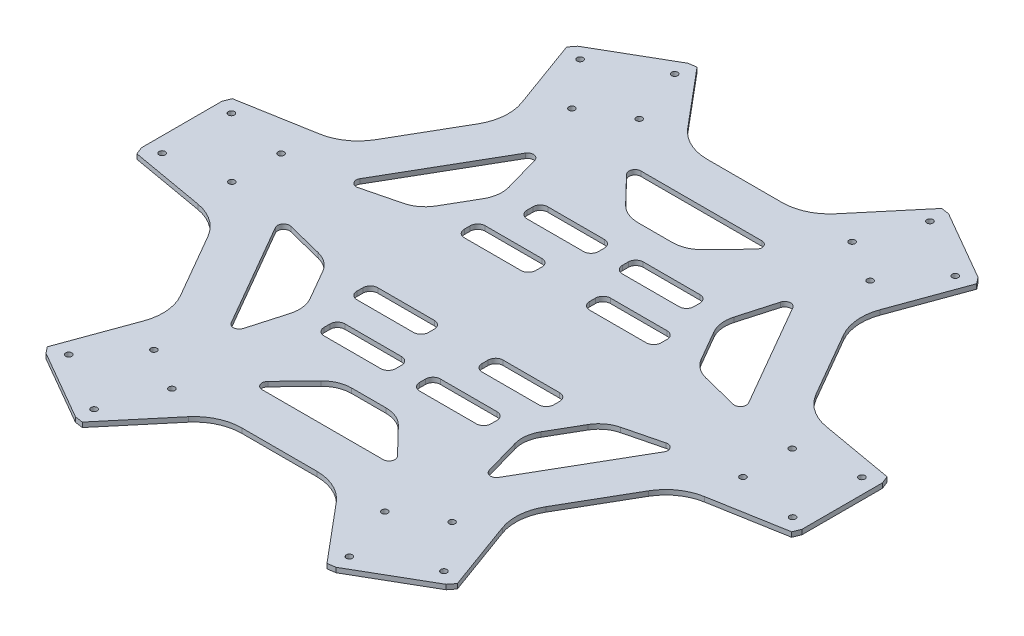
SolidWorks part; units mm, degrees
ref_plane "Front Plane" through (0, 0, 0) normal (0, 0, 1) x (1, 0, 0)
ref_plane "Top Plane" through (0, 0, 0) normal (0, 1, 0) x (1, 0, 0)
ref_plane "Right Plane" through (0, 0, 0) normal (1, 0, 0) x (0, 0, -1)
sketch "Sketch2" plane through (0, 0, 0) normal (0, 1, 0) x (1, 0, 0)
  line L0 (-110.75, -13.5) -> (-110.75, 13.5)
  line L1 (110.75, 0) -> (55.375, 95.9123) construction
  line L2 (55.375, 95.9123) -> (-55.375, 95.9123) construction
  line L3 (-55.375, 95.9123) -> (-110.75, 0) construction
  line L4 (-110.75, 0) -> (-55.375, -95.9123) construction
  line L5 (-55.375, -95.9123) -> (55.375, -95.9123) construction
  line L6 (55.375, -95.9123) -> (110.75, 0) construction
  line L7 (-110.75, 0) -> (0, 0) construction
  line L14 (0, 0) -> (0, 78) construction
  line L15 (-67.55, 39) -> (-90.0666, 0) construction
  line L16 (0, 78) -> (-67.55, 39) construction
  line L17 (-67.55, 39) -> (-67.55, -39) construction
  line L18 (-67.55, -39) -> (0, -78) construction
  line L19 (0, -78) -> (67.55, -39) construction
  line L20 (67.55, -39) -> (67.55, 39) construction
  line L21 (67.55, 39) -> (0, 78) construction
  line L22 (-110.75, 13.5) -> (-109.75, 13.5) construction
  line L23 (-67.55, 39) -> (-77.5583, 21.6651)
  line L24 (-109.75, 13.5) -> (-109.75, 16) construction
  line L25 (-110.75, 13.5) -> (-109.75, 16)
  line L26 (-77.5583, 21.6651) -> (-78.8083, 19.5) construction
  line L27 (-109.75, 16) -> (-77.5583, 21.6651)
  line L28 (-110.75, -13.5) -> (-109.75, -16)
  line L29 (-109.75, -16) -> (-77.5583, -21.6651)
  line L30 (-67.55, -39) -> (-77.5583, -21.6651)
  line L31 (-67.55, 39) -> (-57.5417, 56.3349)
  line L32 (-68.7314, 87.0463) -> (-57.5417, 56.3349)
  line L33 (-67.0663, 89.1623) -> (-68.7314, 87.0463)
  line L34 (-67.0663, 89.1623) -> (-43.6837, 102.6623)
  line L35 (-43.6837, 102.6623) -> (-41.0186, 103.0463)
  line L36 (-41.0186, 103.0463) -> (-20.0167, 78)
  line L37 (0, 78) -> (-20.0167, 78)
  line L38 (0, 78) -> (20.0167, 78)
  line L39 (41.0186, 103.0463) -> (20.0167, 78)
  line L40 (43.6837, 102.6623) -> (41.0186, 103.0463)
  line L41 (43.6837, 102.6623) -> (67.0663, 89.1623)
  line L42 (67.0663, 89.1623) -> (68.7314, 87.0463)
  line L43 (68.7314, 87.0463) -> (57.5417, 56.3349)
  line L44 (67.55, 39) -> (57.5417, 56.3349)
  line L45 (67.55, 39) -> (77.5583, 21.6651)
  line L46 (109.75, 16) -> (77.5583, 21.6651)
  line L47 (110.75, 13.5) -> (109.75, 16)
  line L48 (110.75, 13.5) -> (110.75, -13.5)
  line L49 (110.75, -13.5) -> (109.75, -16)
  line L50 (109.75, -16) -> (77.5583, -21.6651)
  line L51 (67.55, -39) -> (77.5583, -21.6651)
  line L52 (67.55, -39) -> (57.5417, -56.3349)
  line L53 (68.7314, -87.0463) -> (57.5417, -56.3349)
  line L54 (67.0663, -89.1623) -> (68.7314, -87.0463)
  line L55 (67.0663, -89.1623) -> (43.6837, -102.6623)
  line L56 (43.6837, -102.6623) -> (41.0186, -103.0463)
  line L57 (41.0186, -103.0463) -> (20.0167, -78)
  line L58 (0, -78) -> (20.0167, -78)
  line L59 (0, -78) -> (-20.0167, -78)
  line L60 (-41.0186, -103.0463) -> (-20.0167, -78)
  line L61 (-43.6837, -102.6623) -> (-41.0186, -103.0463)
  line L62 (-43.6837, -102.6623) -> (-67.0663, -89.1623)
  line L63 (-67.0663, -89.1623) -> (-68.7314, -87.0463)
  line L64 (-68.7314, -87.0463) -> (-57.5417, -56.3349)
  line L65 (-67.55, -39) -> (-57.5417, -56.3349)
  circle A0 centre (0, 0) radius 95.9123 construction
  circle A1 centre (0, 0) radius 67.55 construction
  point P67 (0, 0)
  dimension "D1" = 110.75
  dimension "D2" = 13.5
  dimension "D3" = 78
  dimension "D4" = 1
  dimension "D5" = 2.5
  dimension "D6" = 2.5
  dimension "D7" = 6
extrude "Base plate" add sketch "Sketch2" along normal blind 1.6 contours L30 L65 L64 L63 L62 L61 L60 L59 L58 L57 L56 L55 L54 L53 L52 L51 L50 L49 L48 L47 L46 L45 L44 L43 L42 L41 L40 L39 L38 L37 L36 L35 L34 L33 L32 L31 L23 L27 L25 L0 L28 L29 region at (0, 0, 0)
fillet "Fillet3" radius 16 12 edges at (-57.5417, 0.8, 56.3349) (-77.5583, 0.8, 21.6651) (-20.0167, 0.8, 78) (20.0167, 0.8, 78) (57.5417, 0.8, 56.3349) (77.5583, 0.8, 21.6651) (77.5583, 0.8, -21.6651) (57.5417, 0.8, -56.3349) (20.0167, 0.8, -78) (-20.0167, 0.8, -78) (-57.5417, 0.8, -56.3349) (-77.5583, 0.8, -21.6651)
sketch "Sketch3" plane through (0, 1.6, 0) normal (0, 1, 0) x (1, 0, 0)
  line L0 (-55.375, 95.9123) -> (-65.4209, 90.1123) construction
  line L1 (-67.0663, 89.1623) -> (-43.6837, 102.6623) construction
  line L2 (-65.4209, 90.1123) -> (-62.8859, 85.7216) construction
  line L3 (-62.8859, 85.7216) -> (-42.7941, 97.3216) construction
  line L4 (-62.8859, 85.7216) -> (-52.8859, 68.4011) construction
  line L5 (-52.8859, 68.4011) -> (-49.9847, 70.0761) construction
  line L6 (-49.9847, 70.0761) -> (-35.6953, 78.3261) construction
  dimension "D1" = 11.6
  dimension "D2" = 5.07
  dimension "D3" = 23.2
  dimension "D4" = 20
  dimension "D5" = 3.35
  dimension "D6" = 16.5
hole_wizard "M2.5x0.45 Tapped Hole1" positions "Sketch4" profile "Sketch5" tap size "M2.5x0.45" standard "ANSI Metric"
sketch "Sketch4" plane through (0, 1.6, 0) normal (0, 1, 0) x (1, 0, 0)
  point P0 (-62.8859, 85.7216)
  point P3 (-49.9847, 70.0761)
  point P6 (-35.6953, 78.3261)
  point P9 (-42.7941, 97.3216)
sketch "Sketch5" plane through (-62.8859, 1.6, -85.7216) normal (1, 0, 0) x (0, 0, 1)
  line L0 (0, 0) -> (0, 6.9659)
  line L1 (0, 6.9659) -> (1.025, 6.35)
  line L2 (1.025, 6.35) -> (1.025, 0)
  line L5 (1.025, 0) -> (0, 0)
  line L10 (0, 6.9659) -> (-1.025, 6.35) construction
  line L11 (0, -6.35) -> (0, 107.95) construction
  dimension "Tap Drill Dia." = 2.05
  dimension "Tap Drill Depth" = 6.35
  dimension "Drill Angle" = 118
sketch "Sketch6" plane through (0, 0, 0) normal (0, 0, 1) x (1, 0, 0)
  line L0 (0, 0) -> (0, 50) construction
  dimension "D1" = 50
pattern_circular "CirPattern1" count 6 over 360 about axis through (0, 0, 0) along (0, 1, 0) of "M2.5x0.45 Tapped Hole1"
sketch "Sketch7" plane through (0, 1.6, 0) normal (0, 1, 0) x (1, 0, 0)
  line L0 (0, 0) -> (0, 48) construction
  line L1 (0, 48) -> (0, 63.5) construction
  line L2 (25, 63.5) -> (-25, 63.5)
  line L3 (10, 48) -> (-10, 48)
  line L4 (-25, 63.5) -> (-10, 48)
  line L5 (25, 63.5) -> (10, 48)
  dimension "D1" = 48
  dimension "D2" = 63.5
  dimension "D3" = 25
  dimension "D4" = 10
extrude "Cut-Extrude1" cut sketch "Sketch7" against normal up to next
fillet "Fillet4" radius 2 2 edges at (-25, 0.8, -63.5) (25, 0.8, -63.5)
fillet "Fillet5" radius 10 2 edges at (10, 0.8, -48) (-10, 0.8, -48)
pattern_circular "CirPattern2" count 6 over 360 about axis through (0, 0, 0) along (0, 1, 0) of "Cut-Extrude1", "Fillet4", "Fillet5" reverse direction yes
sketch "Sketch8" plane through (0, 1.6, 0) normal (0, 1, 0) x (1, 0, 0)
  line L0 (0, 0) -> (0, 34) construction
  line L1 (0, 34) -> (-16, 34) construction
  line L2 (0, 18) -> (-21, 18) construction
  line L3 (33, 21.5) -> (9, 14.5) construction
  line L4 (-28, 37.5) -> (-4, 37.5)
  line L5 (-28, 37.5) -> (-28, 30.5)
  line L6 (-28, 30.5) -> (-4, 30.5)
  line L7 (-4, 37.5) -> (-4, 30.5)
  line L8 (-28, 37.5) -> (-4, 30.5) construction
  line L9 (-28, 30.5) -> (-4, 37.5) construction
  line L10 (-33, 21.5) -> (-9, 21.5)
  line L11 (-33, 21.5) -> (-33, 14.5)
  line L12 (-33, 14.5) -> (-9, 14.5)
  line L13 (-9, 21.5) -> (-9, 14.5)
  line L14 (-33, 21.5) -> (-9, 14.5) construction
  line L15 (-33, 14.5) -> (-9, 21.5) construction
  line L16 (33, 14.5) -> (9, 21.5) construction
  line L17 (28, 30.5) -> (4, 37.5) construction
  line L18 (28, 37.5) -> (4, 30.5) construction
  line L19 (28, 30.5) -> (4, 30.5)
  line L20 (4, 37.5) -> (4, 30.5)
  line L21 (28, 37.5) -> (4, 37.5)
  line L22 (28, 37.5) -> (28, 30.5)
  line L23 (33, 14.5) -> (9, 14.5)
  line L24 (9, 21.5) -> (9, 14.5)
  line L25 (33, 21.5) -> (9, 21.5)
  line L26 (33, 21.5) -> (33, 14.5)
  line L27 (0, 0) -> (-110.75, 0) construction
  line L28 (-110.75, -13.5) -> (-110.75, 13.5) construction
  line L29 (28, -37.5) -> (4, -30.5) construction
  line L30 (28, -30.5) -> (4, -37.5) construction
  line L31 (33, -14.5) -> (9, -21.5) construction
  line L32 (-33, -14.5) -> (-9, -21.5) construction
  line L33 (-33, -21.5) -> (-9, -14.5) construction
  line L34 (-28, -30.5) -> (-4, -37.5) construction
  line L35 (-28, -37.5) -> (-4, -30.5) construction
  line L36 (33, -21.5) -> (9, -14.5) construction
  line L38 (33, -21.5) -> (33, -14.5)
  line L39 (33, -21.5) -> (9, -21.5)
  line L40 (9, -21.5) -> (9, -14.5)
  line L41 (33, -14.5) -> (9, -14.5)
  line L42 (28, -37.5) -> (28, -30.5)
  line L43 (28, -37.5) -> (4, -37.5)
  line L44 (4, -37.5) -> (4, -30.5)
  line L45 (28, -30.5) -> (4, -30.5)
  line L46 (-9, -21.5) -> (-9, -14.5)
  line L47 (-33, -14.5) -> (-9, -14.5)
  line L48 (-33, -21.5) -> (-33, -14.5)
  line L49 (-33, -21.5) -> (-9, -21.5)
  line L50 (-4, -37.5) -> (-4, -30.5)
  line L51 (-28, -30.5) -> (-4, -30.5)
  line L52 (-28, -37.5) -> (-28, -30.5)
  line L53 (-28, -37.5) -> (-4, -37.5)
  dimension "D1" = 34
  dimension "D2" = 16
  dimension "D3" = 18
  dimension "D4" = 21
  dimension "D5" = 7
  dimension "D6" = 24
  dimension "D7" = 24
  dimension "D8" = 7
extrude "Cut-Extrude2" cut sketch "Sketch8" against normal up to next
fillet "Fillet6" radius 2.5 32 edges at (-9, 0.8, -21.5) (-9, 0.8, -14.5) (-33, 0.8, -14.5) (-33, 0.8, -21.5) (-4, 0.8, -30.5) (-28, 0.8, -30.5) (-28, 0.8, -37.5) (-4, 0.8, -37.5) (-9, 0.8, 21.5) (-33, 0.8, 14.5) (-28, 0.8, 30.5) (-4, 0.8, 37.5) (-33, 0.8, 21.5) (-28, 0.8, 37.5) (4, 0.8, 37.5) (9, 0.8, 21.5) (9, 0.8, 14.5) (4, 0.8, 30.5) (-4, 0.8, 30.5) (-9, 0.8, 14.5) (28, 0.8, 30.5) (28, 0.8, 37.5) (33, 0.8, 21.5) (33, 0.8, 14.5) (33, 0.8, -21.5) (28, 0.8, -37.5) (28, 0.8, -30.5) (33, 0.8, -14.5) (4, 0.8, -30.5) (4, 0.8, -37.5) (9, 0.8, -21.5) (9, 0.8, -14.5)
